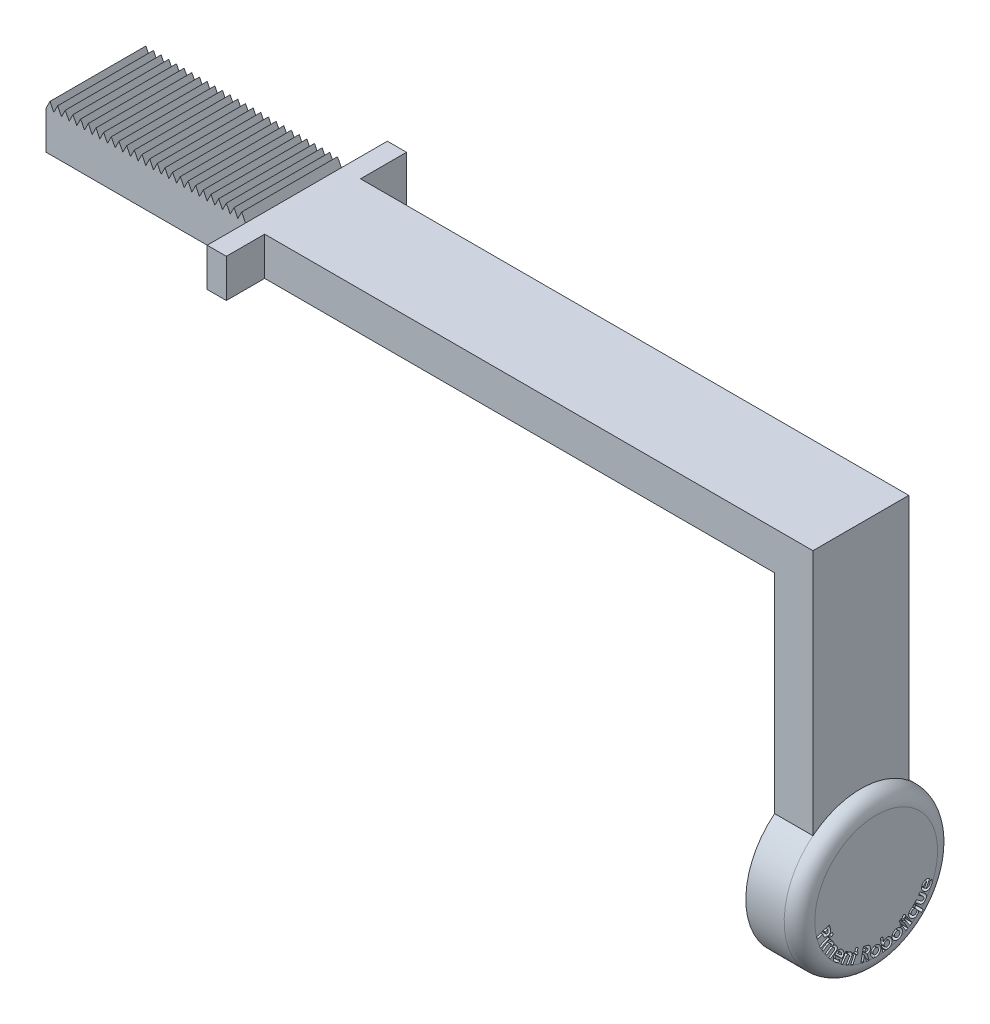
SolidWorks part; units mm, degrees
ref_plane "Plan de face" through (0, 0, 0) normal (0, 0, 1) x (1, 0, 0)
ref_plane "Plan de dessus" through (0, 0, 0) normal (0, 1, 0) x (1, 0, 0)
ref_plane "Plan de droite" through (0, 0, 0) normal (1, 0, 0) x (0, 0, -1)
sketch "Esquisse1" plane through (0, 0, 0) normal (0, 0, 1) x (1, 0, 0)
  line L1 (-194.7011, 1.8406) -> (5.2989, 1.8406)
  line L2 (-194.7011, 1.8406) -> (-194.7011, -8.1594)
  line L3 (-194.7011, -8.1594) -> (5.2989, -8.1594)
  line L4 (5.2989, 1.8406) -> (5.2989, -8.1594)
  line L5 (-194.7011, 1.8406) -> (5.2989, -8.1594) construction
  line L6 (-194.7011, -8.1594) -> (5.2989, 1.8406) construction
  line L7 (5.2989, -8.1594) -> (-4.7011, -8.1594)
  line L8 (5.2989, -8.1594) -> (5.2989, -98.1594)
  line L9 (5.2989, -98.1594) -> (-4.7011, -98.1594)
  line L10 (-4.7011, -8.1594) -> (-4.7011, -98.1594)
  point P0 (-94.7011, -3.1594)
  dimension "D1" = 200
  dimension "D2" = 10
  dimension "D3" = 10
  dimension "D4" = 90
extrude "Boss.-Extru.1" add sketch "Esquisse1" along normal blind 25 contours L4 L1 L2 L3 | L3 L10 L9 L8 region at (-94.7011, -3.1594, 0) region at (0.2989, -53.1594, 0)
ref_plane "Plan1" through (0, 0, 12.5) normal (0, 0, 1) x (1, 0, 0)
sketch "Esquisse2" plane through (0, 0, 12.5) normal (0, 0, 1) x (1, 0, 0)
  line L0 (-194.7011, 1.8406) -> (-193.7011, 3.8406)
  line L1 (-193.7011, 3.8406) -> (-192.7011, 1.8406)
  line L2 (-194.7011, 1.8406) -> (5.2989, 1.8406) construction
  line L3 (-192.7011, 1.8406) -> (-191.7011, 3.8406)
  line L4 (-191.7011, 3.8406) -> (-190.7011, 1.8406)
  line L5 (-192.7011, 1.8406) -> (-194.7011, 1.8406)
  line L6 (-190.7011, 1.8406) -> (-192.7011, 1.8406)
  line L43 (-188.7011, 1.8406) -> (-190.7011, 1.8406)
  line L48 (-190.7011, 1.8406) -> (-189.7011, 3.8406)
  line L49 (-189.7011, 3.8406) -> (-188.7011, 1.8406)
  line L50 (-188.7011, 1.8406) -> (-187.7011, 3.8406)
  line L51 (-187.7011, 3.8406) -> (-186.7011, 1.8406)
  line L52 (-186.7011, 1.8406) -> (-188.7011, 1.8406)
  line L53 (-184.7011, 1.8406) -> (-186.7011, 1.8406)
  line L54 (-186.7011, 1.8406) -> (-185.7011, 3.8406)
  line L55 (-185.7011, 3.8406) -> (-184.7011, 1.8406)
  line L56 (-184.7011, 1.8406) -> (-183.7011, 3.8406)
  line L57 (-183.7011, 3.8406) -> (-182.7011, 1.8406)
  line L58 (-182.7011, 1.8406) -> (-184.7011, 1.8406)
  line L59 (-180.7011, 1.8406) -> (-182.7011, 1.8406)
  line L60 (-182.7011, 1.8406) -> (-181.7011, 3.8406)
  line L61 (-181.7011, 3.8406) -> (-180.7011, 1.8406)
  line L62 (-180.7011, 1.8406) -> (-179.7011, 3.8406)
  line L63 (-179.7011, 3.8406) -> (-178.7011, 1.8406)
  line L64 (-178.7011, 1.8406) -> (-180.7011, 1.8406)
  line L65 (-176.7011, 1.8406) -> (-178.7011, 1.8406)
  line L66 (-178.7011, 1.8406) -> (-177.7011, 3.8406)
  line L67 (-177.7011, 3.8406) -> (-176.7011, 1.8406)
  line L68 (-176.7011, 1.8406) -> (-175.7011, 3.8406)
  line L69 (-175.7011, 3.8406) -> (-174.7011, 1.8406)
  line L70 (-174.7011, 1.8406) -> (-176.7011, 1.8406)
  line L71 (-172.7011, 1.8406) -> (-174.7011, 1.8406)
  line L72 (-174.7011, 1.8406) -> (-173.7011, 3.8406)
  line L73 (-173.7011, 3.8406) -> (-172.7011, 1.8406)
  line L74 (-172.7011, 1.8406) -> (-171.7011, 3.8406)
  line L75 (-171.7011, 3.8406) -> (-170.7011, 1.8406)
  line L76 (-170.7011, 1.8406) -> (-172.7011, 1.8406)
  line L77 (-168.7011, 1.8406) -> (-170.7011, 1.8406)
  line L78 (-170.7011, 1.8406) -> (-169.7011, 3.8406)
  line L79 (-169.7011, 3.8406) -> (-168.7011, 1.8406)
  line L80 (-168.7011, 1.8406) -> (-167.7011, 3.8406)
  line L81 (-167.7011, 3.8406) -> (-166.7011, 1.8406)
  line L82 (-166.7011, 1.8406) -> (-168.7011, 1.8406)
  line L83 (-164.7011, 1.8406) -> (-166.7011, 1.8406)
  line L84 (-166.7011, 1.8406) -> (-165.7011, 3.8406)
  line L85 (-165.7011, 3.8406) -> (-164.7011, 1.8406)
  line L86 (-164.7011, 1.8406) -> (-163.7011, 3.8406)
  line L87 (-163.7011, 3.8406) -> (-162.7011, 1.8406)
  line L88 (-162.7011, 1.8406) -> (-164.7011, 1.8406)
  line L89 (-160.7011, 1.8406) -> (-162.7011, 1.8406)
  line L90 (-162.7011, 1.8406) -> (-161.7011, 3.8406)
  line L91 (-161.7011, 3.8406) -> (-160.7011, 1.8406)
  line L92 (-160.7011, 1.8406) -> (-159.7011, 3.8406)
  line L93 (-159.7011, 3.8406) -> (-158.7011, 1.8406)
  line L94 (-158.7011, 1.8406) -> (-160.7011, 1.8406)
  line L95 (-156.7011, 1.8406) -> (-158.7011, 1.8406)
  line L96 (-158.7011, 1.8406) -> (-157.7011, 3.8406)
  line L97 (-157.7011, 3.8406) -> (-156.7011, 1.8406)
  line L98 (-156.7011, 1.8406) -> (-155.7011, 3.8406)
  line L99 (-155.7011, 3.8406) -> (-154.7011, 1.8406)
  line L100 (-154.7011, 1.8406) -> (-156.7011, 1.8406)
  line L101 (-152.7011, 1.8406) -> (-154.7011, 1.8406)
  line L102 (-154.7011, 1.8406) -> (-153.7011, 3.8406)
  line L103 (-153.7011, 3.8406) -> (-152.7011, 1.8406)
  line L104 (-152.7011, 1.8406) -> (-151.7011, 3.8406)
  line L105 (-151.7011, 3.8406) -> (-150.7011, 1.8406)
  line L106 (-150.7011, 1.8406) -> (-152.7011, 1.8406)
  line L107 (-148.7011, 1.8406) -> (-150.7011, 1.8406)
  line L108 (-150.7011, 1.8406) -> (-149.7011, 3.8406)
  line L109 (-149.7011, 3.8406) -> (-148.7011, 1.8406)
  line L110 (-148.7011, 1.8406) -> (-147.7011, 3.8406)
  line L111 (-147.7011, 3.8406) -> (-146.7011, 1.8406)
  line L112 (-146.7011, 1.8406) -> (-148.7011, 1.8406)
  line L113 (-144.7011, 1.8406) -> (-146.7011, 1.8406)
  line L114 (-146.7011, 1.8406) -> (-145.7011, 3.8406)
  line L115 (-145.7011, 3.8406) -> (-144.7011, 1.8406)
  line L116 (-144.7011, 1.8406) -> (-143.7011, 3.8406)
  line L117 (-143.7011, 3.8406) -> (-142.7011, 1.8406)
  line L118 (-142.7011, 1.8406) -> (-144.7011, 1.8406)
  dimension "D1" = 2
  dimension "D2" = 2
  dimension "D3" = 1
  dimension "D4" = 2
  dimension "D5" = 1
  dimension "D6" = 2
  dimension "D7" = 13
extrude "Boss.-Extru.2" add sketch "Esquisse2" along normal mid plane 25 contours L78 | L71 L73 L72 | L69 | L65 L67 L66 | L63 | L57 | L51 | L43 L49 L48 | L5 L1 L0 | L6 L4 L3 | L74 L75 L76 | L60 L61 L59 | L54 L55 L53 | L80 L81 L82 | L83 L84 L85 | L86 L87 L88 | L89 L90 L91 | L92 L93 L94 | L95 L96 L97 | L98 L99 L100 | L101 L102 L103 | L104 L105 L106 | L107 L108 L109 | L110 L111 L112 | L113 L114 L115 | L116 L117 L118 region at (-169.7011, 2.5073, 12.5) region at (-173.7011, 2.5073, 12.5) region at (-175.7011, 2.5073, 12.5) region at (-177.7011, 2.5073, 12.5) region at (-179.7011, 2.5073, 12.5) region at (-183.7011, 2.5073, 12.5) region at (-187.7011, 2.5073, 12.5) region at (-189.7011, 2.5073, 12.5) region at (-191.7011, 2.5073, 12.5) region at (-193.7011, 2.5073, 12.5)
sketch "Esquisse3" plane through (-4.7011, 0, 0) normal (-1, 0, 0) x (0, 0, 1)
  line L0 (12.5, -45.1) -> (12.5, 45.1) construction
  line L1 (25, -98.1594) -> (0, -98.1594) construction
  circle A0 centre (12.5, -78.1594) radius 20
  circle A1 centre (12.5, -78.1594) radius 15
  dimension "D1" = 40
  dimension "D2" = 20
  dimension "D3" = 30
extrude "Boss.-Extru.3" add sketch "Esquisse3" against normal blind 10
sketch "Esquisse4" plane through (-4.7011, 0, 0) normal (-1, 0, 0) x (0, 0, 1)
  circle A0 centre (12.5, -78.1594) radius 20
  circle A1 centre (12.5, -78.1594) radius 15
  circle A2 centre (12.5, -78.1594) radius 24.6712
  line M5 (0, -93.7719) -> (0, -98.1594)
  line M6 (0, -98.1594) -> (25, -98.1594)
  line M7 (25, -98.1594) -> (25, -93.7719)
  line M11 (0, -69.8678) -> (0, -86.451)
  line M14 (25, -86.451) -> (25, -69.8678)
extrude "Enlèv. mat.-Extru.1" cut sketch "Esquisse4" against normal through all contours A1 M14 M11 | A0 M6 M7 | A0 M5 M6 region at (-4.7011, -96.8722, 3.0523) region at (-4.7011, -96.8722, 21.9477) region at (-4.7011, -78.1594, 12.5)
sketch "Esquisse5" plane through (-194.7011, 0, 0) normal (-1, 0, 0) x (0, 0, 1)
  line L0 (25, -8.1594) -> (0, -8.1594) construction
  line L1 (7.5, -8.1594) -> (17.5, -8.1594)
  line L2 (7.5, -8.1594) -> (7.5, -3.1594)
  line L3 (7.5, -3.1594) -> (17.5, -3.1594)
  line L4 (17.5, -8.1594) -> (17.5, -3.1594)
  line L5 (0, 1.8406) -> (0, -8.1594) construction
  dimension "D1" = 7.5
  dimension "D2" = 10
  dimension "D3" = 5
extrude "Enlèv. mat.-Extru.2" cut sketch "Esquisse5" against normal blind 190
sketch "Esquisse6" plane through (5.2989, 0, 0) normal (1, 0, 0) x (0, 0, -1)
  circle A0 centre (-12.5, -78.1594) radius 20
extrude "Boss.-Extru.4" add sketch "Esquisse6" along normal blind 4
fillet "Congé1" radius 4 1 edges at (9.2989, -58.1594, 12.5)
sketch "Esquisse7" plane through (9.2989, 0, 0) normal (1, 0, 0) x (0, 0, -1)
  text T0 "<b>Piment Robotique </b>"
extrude "Enlèv. mat.-Extru.3" cut sketch "Esquisse7" against normal blind 2
sketch "Esquisse8" plane through (-194.7011, 0, 0) normal (-1, 0, 0) x (0, 0, 1)
  line L0 (12.5, 1.8406) -> (12.5, -3.1594) construction
  line L1 (25, 1.8406) -> (0, 1.8406) construction
  line L2 (17.5, -3.1594) -> (7.5, -3.1594) construction
  circle A0 centre (12.5, -0.6594) radius 2
  dimension "D1" = 4
extrude "Enlèv. mat.-Extru.4" cut sketch "Esquisse8" against normal blind 6
sketch "Esquisse9" plane through (5.2989, 0, 0) normal (-1, 0, 0) x (0, 0, 1)
  point P0 (12.5, -78.1594)
sketch "Esquisse10" plane through (0, 0, 25) normal (0, 0, 1) x (1, 0, 0)
  line L0 (-194.7011, -8.1594) -> (-4.7011, -8.1594) construction
  line L3 (-142.7011, -8.1594) -> (-137.7011, -8.1594)
  line L4 (-137.7011, 1.8406) -> (-137.7011, -8.1594)
  line L5 (-142.7011, -8.1594) -> (-142.7011, 1.8406)
  line L6 (-142.7011, 1.8406) -> (-137.7011, 1.8406)
extrude "Boss.-Extru.5" add sketch "Esquisse10" along normal blind 10
sketch "Esquisse11" plane through (0, 0, 0) normal (0, 0, -1) x (-1, 0, 0)
  line L0 (137.7011, -8.1594) -> (137.7011, -13.1594)
  line L1 (142.7011, 1.8406) -> (137.7011, 1.8406)
  line L2 (142.7011, 1.8406) -> (142.7011, -8.1594)
  line L4 (137.7011, 1.8406) -> (137.7011, -8.1594)
  line L5 (137.7011, -13.1594) -> (142.7011, -13.1594)
  line L6 (142.7011, -13.1594) -> (142.7011, -8.1594)
  dimension "D1" = 5
  dimension "D2" = 5
extrude "Boss.-Extru.6" add sketch "Esquisse11" along normal blind 12
